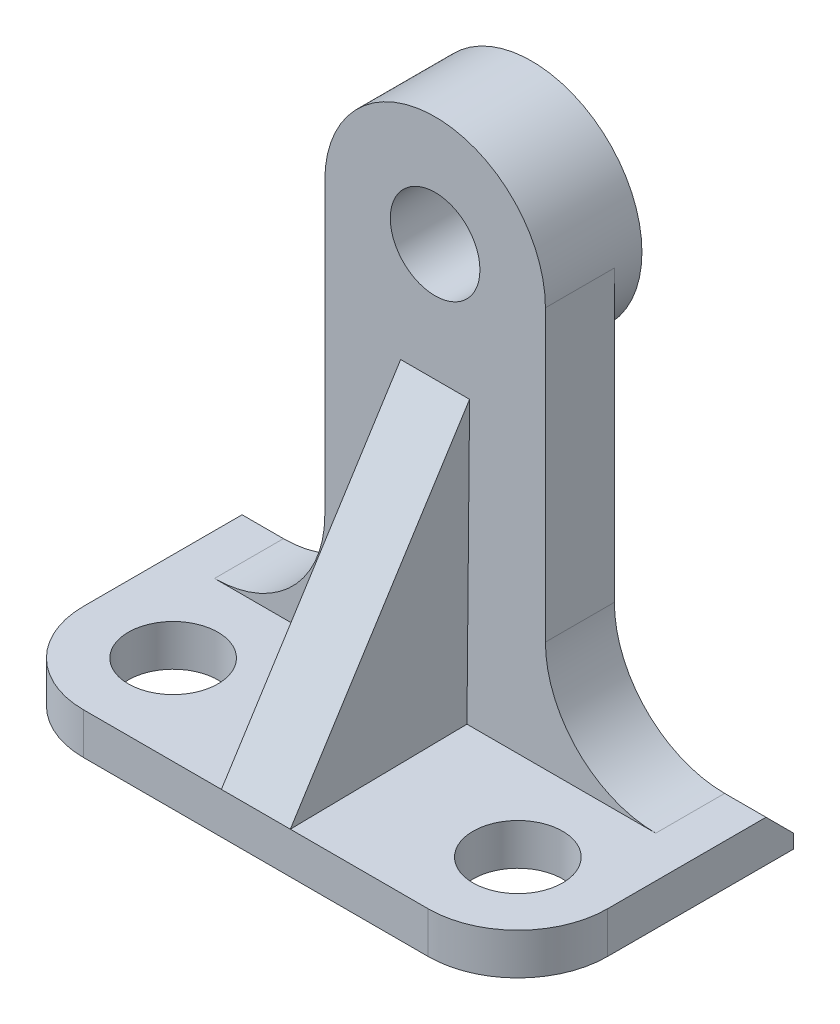
SolidWorks part; units mm, degrees
ref_plane "Alzado" through (0, 0, 0) normal (0, 0, 1) x (1, 0, 0)
ref_plane "Planta" through (0, 0, 0) normal (0, 1, 0) x (1, 0, 0)
ref_plane "Vista lateral" through (0, 0, 0) normal (1, 0, 0) x (0, 0, -1)
sketch "Croquis1" plane through (0, 0, 0) normal (0, 0, 1) x (1, 0, 0)
  line L0 (-16, 0) -> (-16, -42)
  line L1 (16, 0) -> (16, -42)
  line L2 (32, -58) -> (38, -58)
  line L3 (-38, -64) -> (38, -64)
  line L4 (-38, -64) -> (-38, -58)
  line L5 (38, -64) -> (38, -58)
  line L6 (-38, -58) -> (-32, -58)
  arc A0 (16, 0) -> (-16, 0) centre (0, 0) ccw
  circle A1 centre (0, 0) radius 6.5
  arc A2 (-32, -58) -> (-16, -42) centre (-32, -42) ccw
  arc A3 (16, -42) -> (32, -58) centre (32, -42) ccw
  dimension "D1" = 32
  dimension "D2" = 13
  dimension "D3" = 32
  dimension "D7" = 6
  dimension "D8" = 6
  dimension "D9" = 76
extrude "Saliente-Extruir1" add sketch "Croquis1" along normal blind 10
sketch "Croquis2" plane through (0, 0, 0) normal (0, 0, -1) x (-1, 0, 0)
  circle A0 centre (0, 0) radius 16
  dimension "D1" = 32
extrude "Saliente-Extruir2" add sketch "Croquis2" along normal blind 4
sketch "Croquis3" plane through (0, 0, -4) normal (0, 0, -1) x (-1, 0, 0)
  circle A0 centre (0, 0) radius 6.5
  dimension "D1" = 13
extrude "Cortar-Extruir1" cut sketch "Croquis3" against normal blind 4
sketch "Croquis4" plane through (0, -64, 0) normal (0, -1, 0) x (1, 0, 0)
  line L0 (38, 0) -> (38, 36)
  line L2 (38, 36) -> (-38, 36)
  line L3 (38, 0) -> (38, -4)
  line L4 (-38, 36) -> (-38, -4)
  line L5 (-38, -4) -> (38, -4)
  dimension "D1" = 36
  dimension "D2" = 4
  dimension "D3" = 76
  dimension "D4" = 40
extrude "Saliente-Extruir3" add sketch "Croquis4" against normal blind 6
sketch "Croquis5" plane through (0, 0, 0) normal (1, 0, 0) x (0, 0, -1)
  line L0 (-36, -58) -> (-10, -17)
  line L1 (-10, -42) -> (-10, 0) construction
  dimension "D1" = 47
rib "Nervio1" sketch "Croquis5" sketch "Croquis5" thickness 10 extrusion direction parallel to sketch draft on yes draft angle 1 parameters "D1"=10, "D3"=1
chamfer "Chaflán3" distance 4 angle 45 1 edges at (0, -58, -4)
fillet "Redondeo1" radius 13 1 edges at (-38, -61, 36)
fillet "Redondeo2" radius 13 1 edges at (38, -61, 36)
sketch "Croquis6" plane through (0, -58, 0) normal (0, 1, 0) x (1, 0, 0)
  line L0 (0, -36) -> (-25, -36) construction
  line L1 (5, -36) -> (-5, -36) construction
  line L2 (-5, -36) -> (-25, -36) construction
  circle A0 centre (-25, -23) radius 6.5
  circle A1 centre (25, -23) radius 6.5
  dimension "D2" = 13
  dimension "D3" = 13
  dimension "D1" = 25
extrude "Cortar-Extruir2" cut sketch "Croquis6" against normal blind 6
